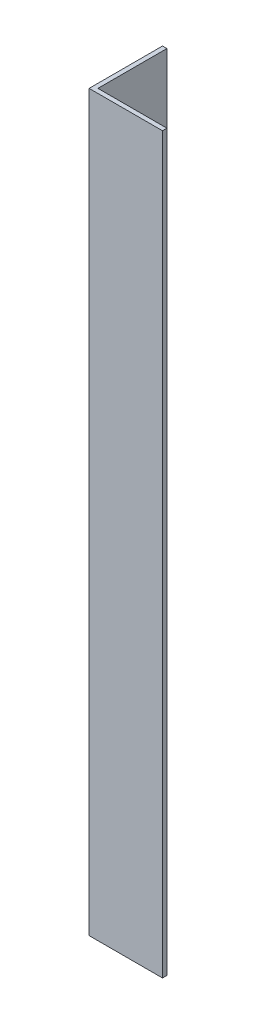
SolidWorks part; units mm, degrees
ref_plane "Спереди" through (0, 0, 0) normal (0, 0, 1) x (1, 0, 0)
ref_plane "Сверху" through (0, 0, 0) normal (0, 1, 0) x (1, 0, 0)
ref_plane "Справа" through (0, 0, 0) normal (1, 0, 0) x (0, 0, -1)
sketch "Эскиз1" plane through (0, 0, 0) normal (0, 1, 0) x (1, 0, 0)
  line L0 (0, 50) -> (0, 0)
  line L1 (0, 0) -> (50, 0)
extrude "Вытянуть-Тонкостенный1" add sketch "Эскиз1" along normal blind 500 thin thin type one direction reverse wall 3
